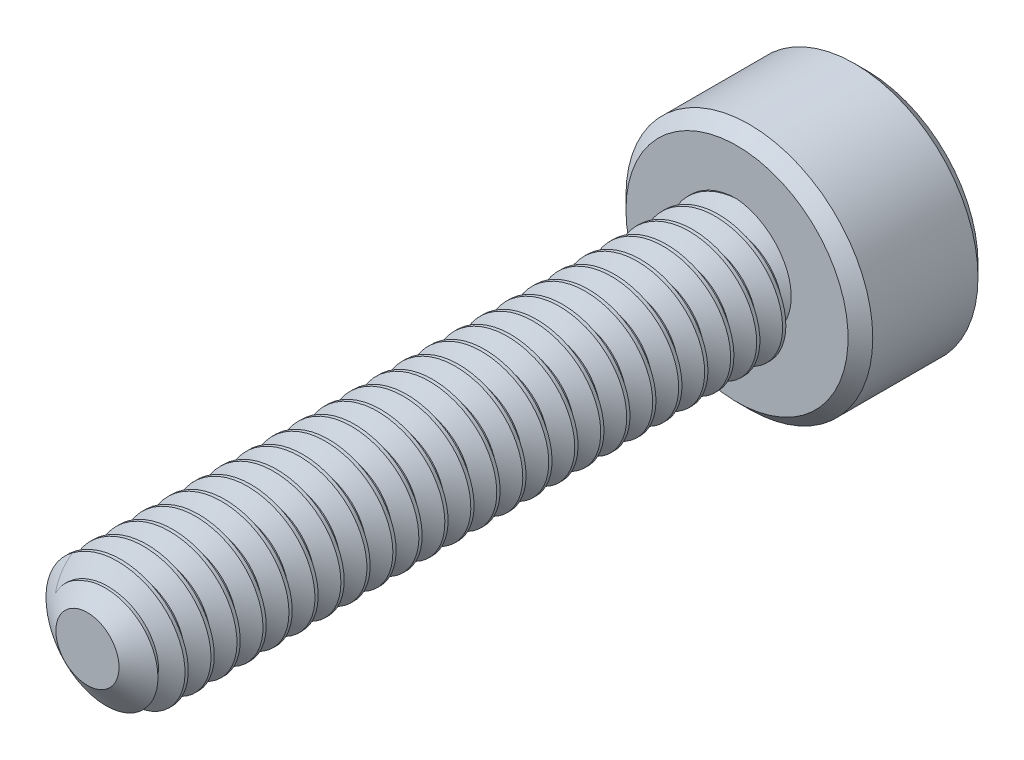
SolidWorks part; units mm, degrees
other "DetailItem1"
ref_plane "Front Plane" through (0, 0, 0) normal (0, 0, 1) x (1, 0, 0)
ref_plane "Top Plane" through (0, 0, 0) normal (0, 1, 0) x (1, 0, 0)
ref_plane "Right Plane" through (0, 0, 0) normal (1, 0, 0) x (0, 0, -1)
sketch "Sketch1" plane through (0, 0, 0) normal (0, 0, 1) x (1, 0, 0)
  circle A0 centre (0, 0) radius 1
  dimension "OD" = 2
extrude "Extrude1" add sketch "Sketch1" against normal blind 10
sketch "Sketch2" plane through (0, 0, 0) normal (0, 0, 1) x (1, 0, 0)
  circle A0 centre (0, 0) radius 1 construction
  circle A1 centre (0, 0) radius 1
curve "Helix/Spiral1" pitch 0.4 height 10.4 radius 1 centre (0, 0, 0) axis (0, 0, -1) start towards (0, 1, 0) parameters "pitch"=0.4
sketch "Sketch3" plane through (0, 0, 0) normal (1, 0, 0) x (0, 0, -1)
  line L0 (-0.35, 1) -> (-0.2, 0.7402)
  line L1 (-0.2, 0.7402) -> (-0.15, 0.7402)
  line L2 (-0.15, 0.7402) -> (0, 1)
  line L3 (-0.35, 1) -> (0, 1)
  line L4 (-0.175, 1) -> (-0.175, 0.7402) construction
  line L5 (-0.275, 0.8701) -> (-0.075, 0.8701) construction
  line L6 (0, 1) -> (0, -1) construction
  dimension "D1" = 0.05
  dimension "D2" = 0.2
  dimension "D3" = 60
sweep "Cut-Sweep1" cut profiles "Sketch3" path "Helix/Spiral1" align with end faces yes
sketch "Sketch4" plane through (0, 0, 0) normal (1, 0, 0) x (0, 0, -1)
  line L0 (0.3598, 1) -> (0, 0.4862)
  line L1 (0, 0.4862) -> (0, 1)
  line L2 (0.3598, 1) -> (0, 1)
  line L3 (-0.35, 1) -> (0, 1) construction
  line L4 (0, 0) -> (7.0209, 0) construction
  dimension "D1" = 55
  dimension "D2" = 0.254
revolve "Cut-Revolve1" cut sketch "Sketch4" angle 360 about L4
sketch "Sketch6" plane through (0, 0, -10) normal (0, 0, -1) x (-1, 0, 0)
  circle A0 centre (0, 0) radius 1.9
  dimension "head dia" = 3.8
extrude "Extrude2" add sketch "Sketch6" along normal blind 2
sketch "Sketch7" plane through (0, 0, -12) normal (0, 0, -1) x (-1, 0, 0)
  line L1 (0, 0.866) -> (-0.75, 0.433)
  line L2 (-0.75, 0.433) -> (-0.75, -0.433)
  line L3 (-0.75, -0.433) -> (0, -0.866)
  line L4 (0, -0.866) -> (0.75, -0.433)
  line L5 (0.75, -0.433) -> (0.75, 0.433)
  line L6 (0.75, 0.433) -> (0, 0.866)
  circle A0 centre (0, 0) radius 0.75 construction
  dimension "hex dia" = 1.5
extrude "Cut-Extrude1" cut sketch "Sketch7" against normal blind 1.125
sketch "Sketch8" plane through (0, 0, -12) normal (0, 0, -1) x (-1, 0, 0)
  circle A0 centre (0, 0) radius 0.866
extrude "Cut-Extrude2" cut sketch "Sketch8" against normal through all draft 45
chamfer "Chamfer1" distance 0.19 angle 45 2 edges at (-1.9, 0, -12) (-1.9, 0, -10)
sketch "Sketch10" plane through (0, 0, -10) normal (0, 0, 1) x (1, 0, 0)
  circle A1 centre (0, 0) radius 1
  circle A2 centre (0, 0) radius 1
  dimension "D1" = 0
ref_plane "Plane1" through (0, 0, 0) normal (0, 0, 1) x (1, 0, 0)
extrude "partial thread" [suppressed] add sketch "Sketch10" along normal up to surface (2 mm away) separate body up to plane "Plane1"
chamfer "Chamfer2" [suppressed] distance 0.04 angle 45
combine bodies "Combine1" [suppressed] operation type add bodies to combine 107 108
sketch "Sketch9" plane through (0, 0, 0) normal (1, 0, 0) x (0, 0, -1)
  line L0 (0, 1) -> (0, -1) construction
  line L1 (1, 1) -> (1, -1) construction
  dimension "D1" = 1
equation "\"D3@Helix/Spiral1\" = \"screw length@Extrude1\"+\"pitch@Helix/Spiral1\""
equation "\"D1@Sketch3\" = \"pitch@Helix/Spiral1\"*.125"
equation "\"D2@Sketch3\" = \"pitch@Helix/Spiral1\"*.5"
equation "\"D1@Cut-Extrude1\" = \"hex dia@Sketch7\"*.75"
equation "\"D1@Chamfer1\" = \"head dia@Sketch6\"*.05"
equation "\"D1@Sketch9\" = \"pitch@Helix/Spiral1\"*2.5"
equation "\"D1@Chamfer2\"=\"OD@Sketch1\"*.02"
